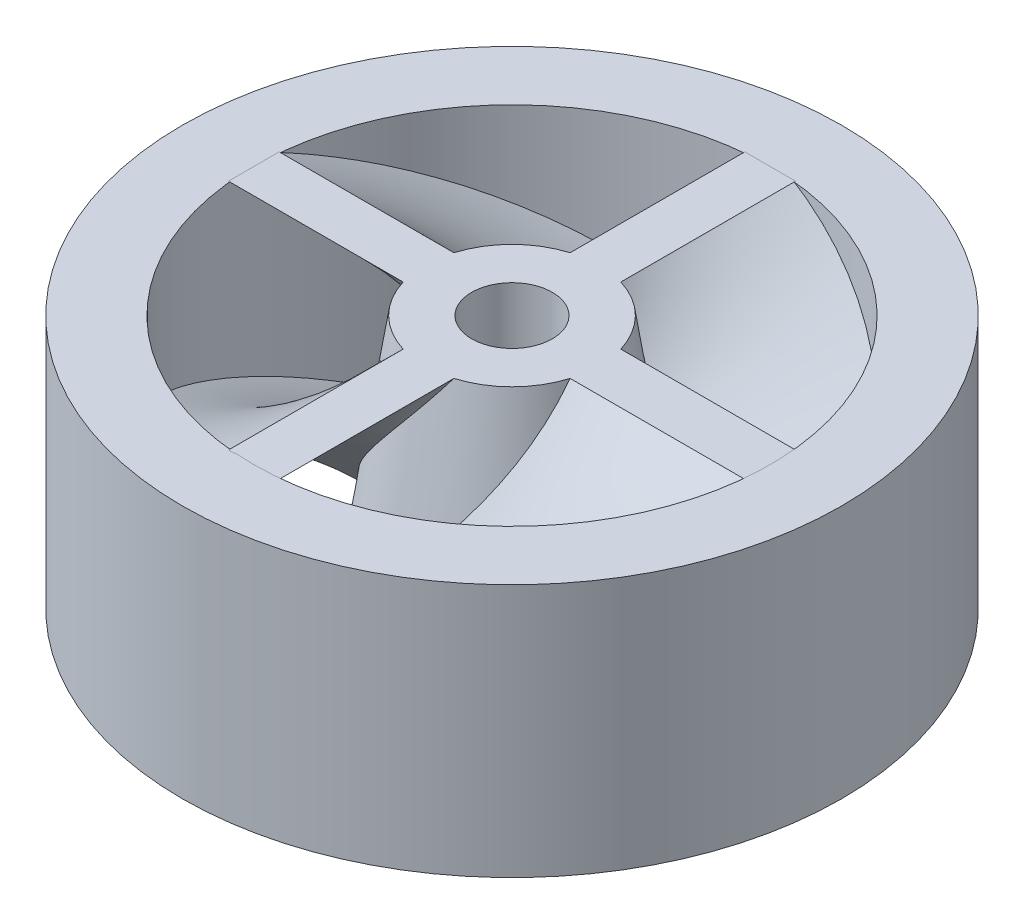
SolidWorks part; units mm, degrees
material "6061-T6 (SS)"
ref_plane "Front Plane" through (0, 0, 0) normal (0, 0, 1) x (1, 0, 0)
ref_plane "Top Plane" through (0, 0, 0) normal (0, 1, 0) x (1, 0, 0)
ref_plane "Right Plane" through (0, 0, 0) normal (1, 0, 0) x (0, 0, -1)
ref_axis "Axis1" through (0, 28.9225, 0) along (0, -1, 0)
sketch "Sketch1" plane through (0, 0, 0) normal (0, 1, 0) x (1, 0, 0)
  circle A0 centre (0, 0) radius 12.9286
  dimension "D1" = 25.8572
curve "Helix/Spiral1" pitch 38.862 height 12.7 radius 12.9286 centre (0, 0, 0) axis (0, -1, 0) start towards (0, 0, 1)
sketch "Sketch2" plane through (0, 0, 0) normal (0, 1, 0) x (1, 0, 0)
  line L0 (-1.27, -12.9286) -> (1.27, -12.9286)
  line L1 (1.27, 0) -> (-1.27, 0)
  line L2 (1.27, 0) -> (1.27, -12.9286)
  line L4 (-1.27, 0) -> (-1.27, -12.9286)
  point P4 (0, -12.9286)
  dimension "D2" = 2.54
  dimension "D1" = 12.9286
sweep "Sweep1" add profiles "Sketch2" path "Helix/Spiral1"
sketch "Sketch4" plane through (0, 0, 0) normal (0, 0, 1) x (1, 0, 0)
  line L0 (0, 0) -> (0, -12.7002)
  line L1 (0, 0) -> (4.3688, 0)
  line L2 (4.3688, 0) -> (6.35, -12.7002)
  line L3 (0, -12.7002) -> (-4.9832, -12.7002) construction
  line L4 (0, -12.7002) -> (6.35, -12.7002)
  spline S0 degree 1 poles (0.5892, -12.7) (-0.5892, -12.7004) knots 0 0 1 1 construction
  dimension "D1" = 4.3688
  dimension "D2" = 6.35
revolve "Revolve1" add sketch "Sketch4" angle 360 about L0
pattern_circular "CirPattern1" count 4 over 360 about axis through (0, 28.9225, 0) along (0, -1, 0) of "Sweep1"
hole_wizard "Tap Drill for #10-32 Tap1" positions "3DSketch2" profile "Sketch9" hole size "#10-32" standard "ANSI Inch" end condition through all
sketch3d "3DSketch2"
  point P0 (0, 0, 0)
sketch "Sketch9" plane through (0, 0, 0) normal (1, 0, 0) x (0, 0, 1)
  line L0 (0, 0) -> (0, 12.7574)
  line L1 (0, 12.7574) -> (2.0193, 12.7574)
  line L2 (2.0193, 12.7574) -> (2.0193, 0)
  line L5 (2.0193, 0) -> (0, 0)
  line L11 (0, -6.35) -> (0, 107.95) construction
  dimension "Thru Hole Dia." = 4.0386
  dimension "Thru Hole Depth" = 12.7574
sketch "Sketch11" plane through (0, 0, 0) normal (0, 0, 1) x (1, 0, 0)
  line L1 (12.9286, 0) -> (16.51, 0)
  line L2 (12.9286, 0) -> (12.9286, -12.7)
  line L3 (12.9286, -12.7) -> (16.51, -12.7)
  line L4 (16.51, 0) -> (16.51, -12.7)
  line L6 (16.51, 0) -> (16.51, 6.1214)
  dimension "D1" = 12.7
  dimension "D2" = 12.9286
  dimension "D3" = 16.51
revolve "Revolve2" add sketch "Sketch11" angle 360 about axis through (0, 28.9225, 0) along (0, -1, 0) region at (14.7193, -6.35, 0)
equation "\"Height\"= 1 / 2"
equation "\"Tip Radius\"= .509"
equation "\"Hub Base Radius\"= .25"
equation "\"Blade Lead\"= 1.53"
equation "\"Axial Clearance\"= .381"
equation "\"D1@Sketch1\"= 2 * \"Tip Radius\""
equation "\"D1@Sketch2\"=\"Tip Radius\""
equation "\"D1@Sketch11\"=\"Height\""
equation "\"D2@Sketch11\"=\"Tip Radius\""
equation "\"Hub Top Radius\"= .172"
equation "\"D1@Sketch4\"=\"Hub Top Radius\""
equation "\"D3@Sketch11\"=\"Inducer OD@[TP] [Pump] [Ox] Pump.Assembly\"/2"
